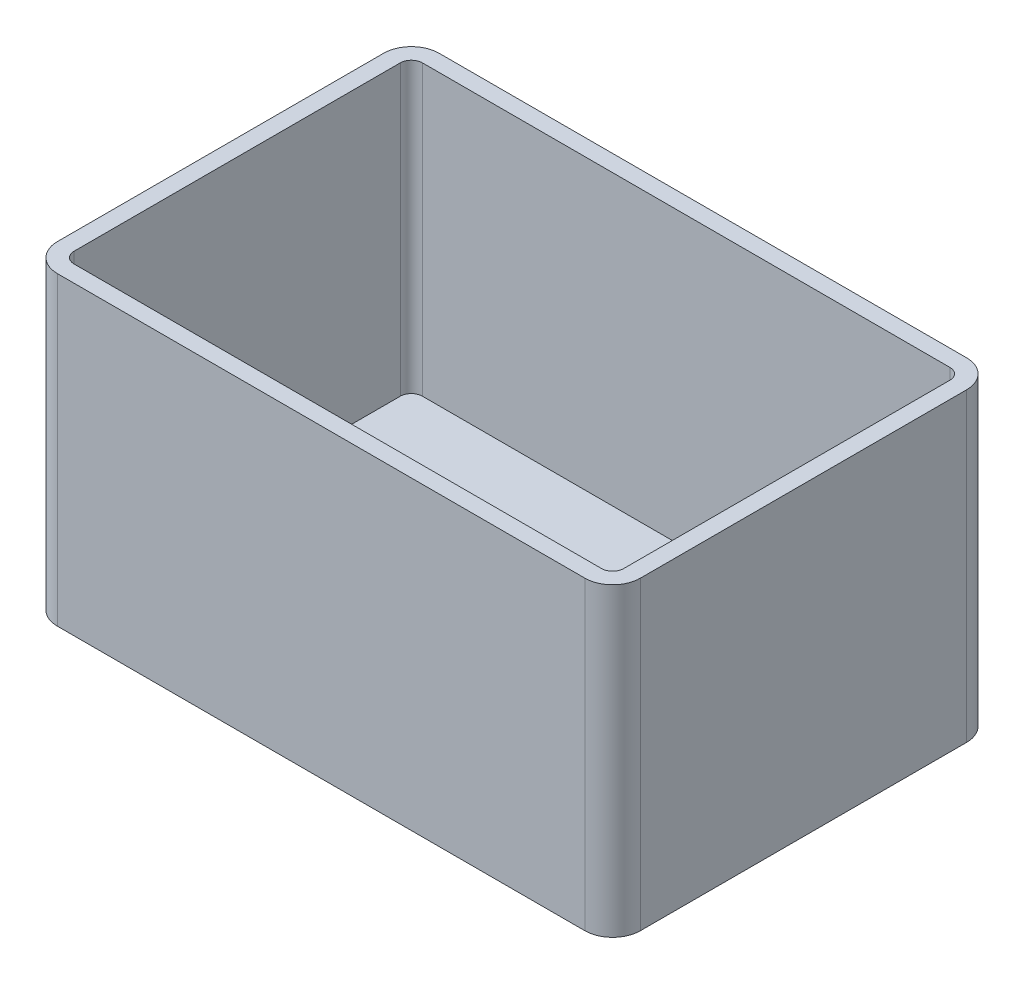
SolidWorks part; units mm, degrees
ref_plane "Front Plane" through (0, 0, 0) normal (0, 0, 1) x (1, 0, 0)
ref_plane "Top Plane" through (0, 0, 0) normal (0, 1, 0) x (1, 0, 0)
ref_plane "Right Plane" through (0, 0, 0) normal (1, 0, 0) x (0, 0, -1)
sketch "Sketch2" plane through (0, 0, 0) normal (0, 1, 0) x (1, 0, 0)
  line L1 (47.5, -34.375) -> (-47.5, -34.375)
  line L2 (52.5, -29.375) -> (52.5, 29.375)
  line L3 (47.5, 34.375) -> (-47.5, 34.375)
  line L4 (-52.5, -29.375) -> (-52.5, 29.375)
  arc A0 (-47.5, -34.375) -> (-52.5, -29.375) centre (-47.5, -29.375) cw
  arc A1 (47.5, -34.375) -> (52.5, -29.375) centre (47.5, -29.375) ccw
  arc A2 (52.5, 29.375) -> (47.5, 34.375) centre (47.5, 29.375) ccw
  arc A3 (-47.5, 34.375) -> (-52.5, 29.375) centre (-47.5, 29.375) ccw
  point P0 (0, 0)
  point P8 (-52.5, -34.375)
  point P13 (52.5, 34.375)
  point P16 (-52.5, 34.375)
  dimension "D3" = 5
  dimension "D1" = 105
  dimension "D2" = 68.75
extrude "Boss-Extrude1" add sketch "Sketch2" along normal blind 55
shell "Shell1" thickness 3 removed face at (0, 55, 0)
sketch "battery_connector_sketch" plane through (0, 3, 0) normal (0, 1, 0) x (1, 0, 0)
  line L0 (-43.2554, -24.8314) -> (-43.2554, -6.8814) construction
  line L1 (-48.2554, -4.8314) -> (-48.2554, -29.1314)
  line L2 (-46.2554, -31.1314) -> (-40.2554, -31.1314)
  line L3 (-40.2554, -2.8314) -> (-46.2554, -2.8314)
  line L4 (-39.5054, -13.4014) -> (-39.5054, -20.5614)
  line L5 (-38.2554, -4.8314) -> (-38.2554, -12.0614)
  line L6 (-38.2554, -29.1314) -> (-38.2554, -21.9014)
  line L7 (-38.2554, -12.0614) -> (-39.5054, -13.4014)
  line L8 (-38.2554, -21.9014) -> (-39.5054, -20.5614)
  line L9 (-41.26, -14.3503) -> (-45.2391, -14.3349)
  arc A0 (-38.2554, -4.8314) -> (-40.2554, -2.8314) centre (-40.2554, -4.8314) ccw
  arc A1 (-48.2554, -29.1314) -> (-46.2554, -31.1314) centre (-46.2554, -29.1314) ccw
  arc A2 (-40.2554, -31.1314) -> (-38.2554, -29.1314) centre (-40.2554, -29.1314) ccw
  arc A3 (-48.2554, -4.8314) -> (-46.2554, -2.8314) centre (-46.2554, -4.8314) cw
  circle A4 centre (-43.2554, -24.8314) radius 2.5
  circle A5 centre (-43.2554, -6.8814) radius 2.5
  arc A6 (-45.2391, -14.3349) -> (-41.26, -14.3503) centre (-43.2554, -15.8564) ccw
  circle A7 centre (-43.2554, -6.8814) radius 2.15
  circle A8 centre (-43.2554, -24.8314) radius 2.15
  dimension "D1" = 4.3
  dimension "D2" = 4.3
extrude "Cut-Extrude1" cut sketch "battery_connector_sketch" against normal blind 2 contours L1 A1 L2 A2 L6 L8 L4 L7 L5 A0 L3 A3
extrude "Cut-Extrude2" cut sketch "battery_connector_sketch<3>" against normal blind 3 contours A7
sketch "battery_connector_sketch<3>" plane through (0, 3, 0) normal (0, 1, 0) x (1, 0, 0) same geometry as "battery_connector_sketch"
extrude "Cut-Extrude3" cut sketch "battery_connector_sketch<4>" against normal blind 3 contours A8
sketch "battery_connector_sketch<4>" plane through (0, 3, 0) normal (0, 1, 0) x (1, 0, 0) same geometry as "battery_connector_sketch"
sketch "Sketch25" plane through (0, 3, 0) normal (0, 1, 0) x (1, 0, 0)
  line L0 (-46.2554, -31.1314) -> (-48.4565, -31.1314)
  line L2 (-46.2554, -2.8314) -> (-49.5, -2.8314)
  line L3 (-49.5, 29.375) -> (-49.5, -29.375) construction
  line L4 (-49.5, -2.8314) -> (-49.5, -29.375)
  line L5 (-48.2554, -29.1314) -> (-48.2554, -4.8314)
  arc A0 (-48.2554, -29.1314) -> (-46.2554, -31.1314) centre (-46.2554, -29.1314) ccw
  arc A1 (-49.5, -29.375) -> (-48.4565, -31.1314) centre (-47.5, -29.375) ccw
  arc A2 (-49.5, -29.375) -> (-47.5, -31.375) centre (-47.5, -29.375) ccw construction
  arc A3 (-48.2554, -4.8314) -> (-46.2554, -2.8314) centre (-46.2554, -4.8314) cw
extrude "Boss-Extrude6" add sketch "Sketch25" along normal blind 12.75
sketch "connector_mount_pins_sockets_sketch" plane through (-48.2554, 0, 0) normal (1, 0, 0) x (0, 0, -1)
  line L0 (-14.1207, 11.25) -> (-8.6541, 11.25) construction
  line L1 (-4.8314, 1) -> (-29.1314, 1) construction
  line L2 (-2.8314, 15.75) -> (-2.8314, 3) construction
  circle A0 centre (-9.8914, 11.25) radius 1.55
  circle A1 centre (-24.0714, 11.25) radius 1.505
  dimension "D1" = 3.1
  dimension "D2" = 10.25
  dimension "D3" = 7.06
extrude "connector_mount_pins_sockets" cut sketch "connector_mount_pins_sockets_sketch" against normal blind 2.4 contours A0 | A1
